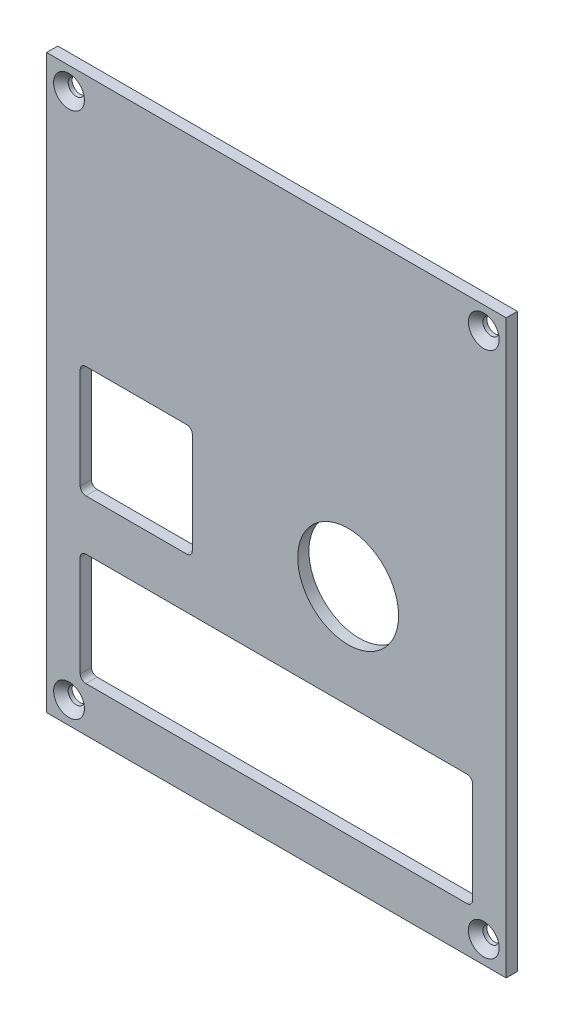
SolidWorks part; units mm, degrees
ref_plane "Front Plane" through (0, 0, 0) normal (0, 0, 1) x (1, 0, 0)
ref_plane "Top Plane" through (0, 0, 0) normal (0, 1, 0) x (1, 0, 0)
ref_plane "Right Plane" through (0, 0, 0) normal (1, 0, 0) x (0, 0, -1)
sketch "Sketch1" plane through (0, 0, 0) normal (0, 0, 1) x (1, 0, 0)
  line L1 (-49.4982, 55.7269) -> (32.5018, 55.7269)
  line L2 (-49.4982, 55.7269) -> (-49.4982, -46.2731)
  line L3 (-49.4982, -46.2731) -> (32.5018, -46.2731)
  line L4 (32.5018, 55.7269) -> (32.5018, -46.2731)
  dimension "D1" = 82
  dimension "D2" = 102
extrude "Boss-Extrude1" add sketch "Sketch1" along normal blind 2
sketch "Sketch2" plane through (0, 0, 2) normal (0, 0, 1) x (1, 0, 0)
  line L3 (-42.4982, -18.2731) -> (25.5018, -18.2731)
  line L4 (-43.4982, -19.2731) -> (-43.4982, -37.2731)
  line L5 (-42.4982, -38.2731) -> (25.5018, -38.2731)
  line L6 (26.5018, -19.2731) -> (26.5018, -37.2731)
  line L7 (-49.4982, 55.7269) -> (-49.4982, -46.2731) construction
  line L8 (-49.4982, -46.2731) -> (32.5018, -46.2731) construction
  line L15 (-42.4982, 10.7269) -> (-24.4982, 10.7269)
  line L16 (-43.4982, 9.7269) -> (-43.4982, -8.2731)
  line L17 (-42.4982, -9.2731) -> (-24.4982, -9.2731)
  line L18 (-23.4982, 9.7269) -> (-23.4982, -8.2731)
  arc A2 (25.5018, -18.2731) -> (26.5018, -19.2731) centre (25.5018, -19.2731) cw
  arc A3 (-43.4982, -37.2731) -> (-42.4982, -38.2731) centre (-42.4982, -37.2731) ccw
  arc A4 (25.5018, -38.2731) -> (26.5018, -37.2731) centre (25.5018, -37.2731) ccw
  arc A5 (-42.4982, -18.2731) -> (-43.4982, -19.2731) centre (-42.4982, -19.2731) ccw
  arc A6 (-43.4982, -8.2731) -> (-42.4982, -9.2731) centre (-42.4982, -8.2731) ccw
  arc A7 (-24.4982, -9.2731) -> (-23.4982, -8.2731) centre (-24.4982, -8.2731) ccw
  arc A8 (-24.4982, 10.7269) -> (-23.4982, 9.7269) centre (-24.4982, 9.7269) cw
  arc A9 (-42.4982, 10.7269) -> (-43.4982, 9.7269) centre (-42.4982, 9.7269) ccw
  circle A11 centre (4.3018, 0.1122) radius 9
  point P11 (26.5018, -18.2731)
  point P14 (-43.4982, -38.2731)
  point P18 (26.5018, -38.2731)
  point P27 (-23.4982, -9.2731)
  point P30 (-23.4982, 10.7269)
  point P33 (-43.4982, 10.7269)
  dimension "D1" = 70
  dimension "D5" = 1
  dimension "D6" = 1
  dimension "D11" = 1
  dimension "D12" = 18
  dimension "D2" = 6
  dimension "D3" = 20
  dimension "D4" = 8
  dimension "D7" = 20
  dimension "D8" = 20
  dimension "D9" = 6
  dimension "D10" = 9
extrude "Cut-Extrude2" cut sketch "Sketch2" against normal blind 2
sketch "Sketch16" plane through (0, 0, 2) normal (0, 0, 1) x (1, 0, 0)
  line L0 (-49.4982, 55.7269) -> (-49.4982, -46.2731) construction
  line L1 (-49.4982, -46.2731) -> (32.5018, -46.2731) construction
  line L2 (32.5018, 55.7269) -> (-49.4982, 55.7269) construction
  line L3 (32.5018, -46.2731) -> (32.5018, 55.7269) construction
  point P0 (-45.4982, -42.2731)
  point P1 (28.5018, -42.2731)
  point P2 (28.5018, 51.7269)
  point P3 (-45.4982, 51.7269)
  point P12 (0, 0)
  point P13 (0, 0)
  point P14 (-48.8946, 47.7821)
  dimension "D1" = 4
  dimension "D2" = 4
  dimension "D3" = 4
  dimension "D4" = 4
  dimension "D5" = 4
  dimension "D6" = 4
  dimension "D7" = 4
  dimension "D8" = 4
hole_wizard "CSK for M2.5 Countersunk Flat Head Screw2" positions "Sketch17" profile "Sketch18" countersink size "M2.5" standard "ISO" end condition through all
sketch "Sketch17" plane through (0, 0, 2) normal (0, 0, 1) x (1, 0, 0)
  point P0 (-45.4982, 51.7269)
  point P3 (-45.4982, -42.2731)
  point P6 (28.5018, -42.2731)
  point P9 (28.5018, 51.7269)
sketch "Sketch18" plane through (-45.4982, 51.7269, 2) normal (1, 0, 0) x (0, -1, 0)
  line L0 (0, 0) -> (0, 2)
  line L1 (0, 2) -> (1.45, 2)
  line L2 (1.45, 2) -> (1.45, 1.3)
  line L3 (1.45, 1.3) -> (2.75, 0)
  line L5 (2.75, 0) -> (0, 0)
  line L6 (-1.45, 1.3) -> (-2.75, 0) construction
  line L11 (0, -6.35) -> (0, 107.95) construction
  dimension "Thru Hole Dia." = 2.9
  dimension "Thru Hole Depth" = 2
  dimension "Near C'Sink Dia." = 5.5
  dimension "Near C'Sink Angle" = 90
